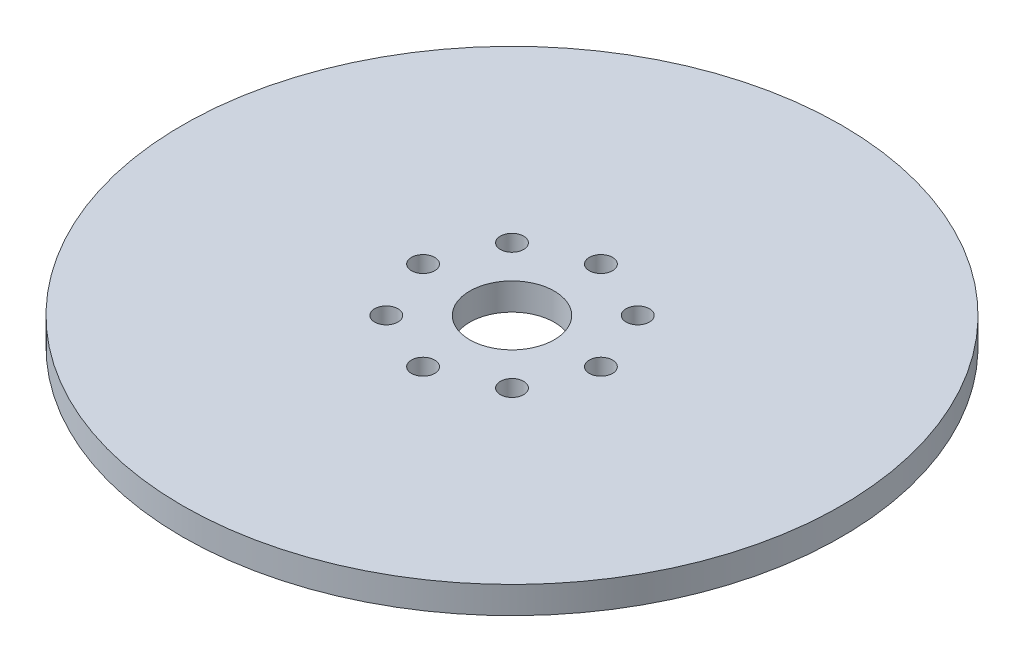
SolidWorks part; units mm, degrees
ref_plane "Front Plane" through (0, 0, 0) normal (0, 0, 1) x (1, 0, 0)
ref_plane "Top Plane" through (0, 0, 0) normal (0, 1, 0) x (1, 0, 0)
ref_plane "Right Plane" through (0, 0, 0) normal (1, 0, 0) x (0, 0, -1)
sketch "Sketch1" plane through (0, 0, 0) normal (0, 1, 0) x (1, 0, 0)
  circle A0 centre (0, 0) radius 97.5
  dimension "FLANGE_OD" = 195
extrude "Boss-Extrude1" add sketch "Sketch1" along normal blind 8
sketch "Sketch2" plane through (0, 0, 0) normal (0, 1, 0) x (1, 0, 0)
  circle A0 centre (0, 0) radius 12.5
  dimension "BORE_D" = 25
extrude "Cut-Extrude1" cut sketch "Sketch2" along normal through all
sketch "Sketch3" plane through (0, 8, 0) normal (0, 1, 0) x (1, 0, 0)
  circle A0 centre (0, 0) radius 26.3055 construction
  circle A1 centre (-26.3055, 0) radius 3.4419
  dimension "BOLT_D" = 6.8838
  dimension "BOLT_PCD" = 52.611
extrude "Cut-Extrude2" cut sketch "Sketch3" against normal blind 5.3392
pattern_circular "CirPattern1" count 8 over 360 about axis through (0, 0, 0) along (0, 1, 0) of "Cut-Extrude2"
